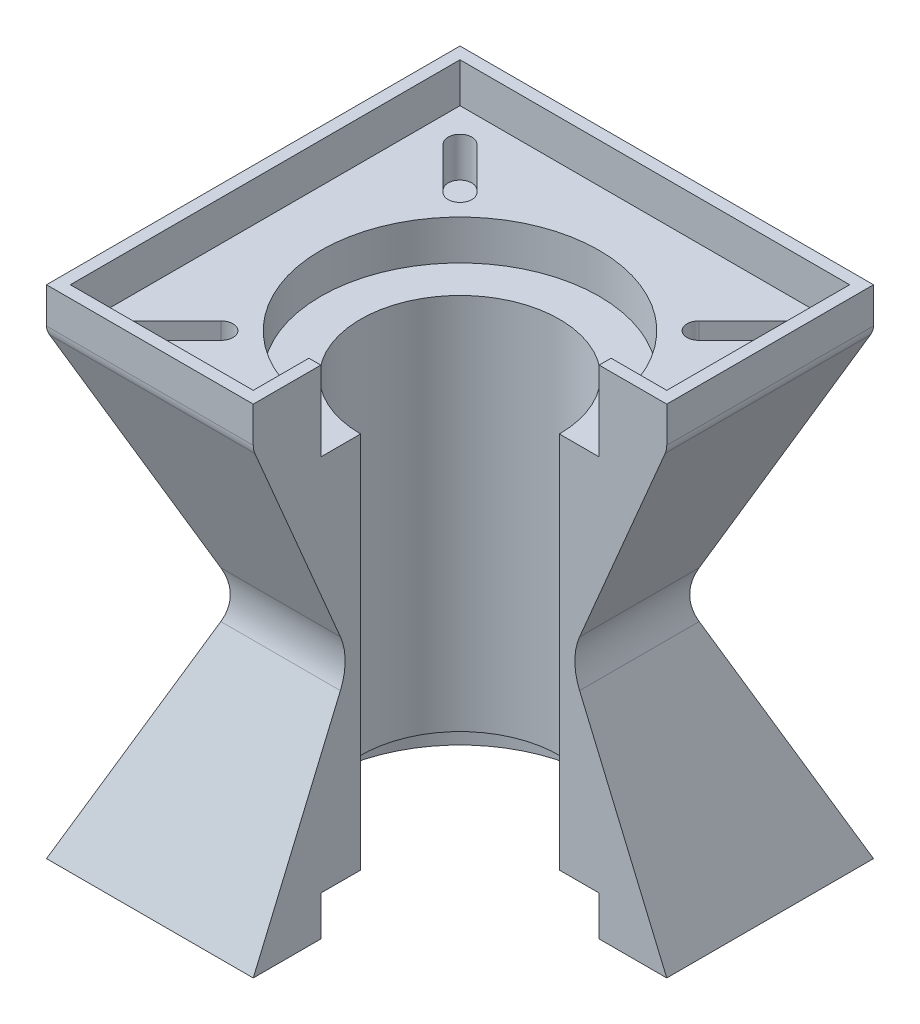
SolidWorks part; units mm, degrees
material "Cast Stainless Steel"
ref_plane "Front Plane" through (0, 0, 0) normal (0, 0, 1) x (1, 0, 0)
ref_plane "Top Plane" through (0, 0, 0) normal (0, 1, 0) x (1, 0, 0)
ref_plane "Right Plane" through (0, 0, 0) normal (1, 0, 0) x (0, 0, -1)
sketch "Sketch1" plane through (0, 0, 0) normal (0, 1, 0) x (1, 0, 0)
  line L1 (-52, 52) -> (52, 52)
  line L2 (-52, 52) -> (-52, -52)
  line L3 (-52, -52) -> (52, -52)
  line L4 (52, 52) -> (52, -52)
  line L5 (-52, 52) -> (52, -52) construction
  line L6 (-52, -52) -> (52, 52) construction
  point P0 (0, 0)
  dimension "D1" = 104
  dimension "D2" = 104
extrude "Boss-Extrude1" add sketch "Sketch1" along normal blind 57.5 draft 23
mirror "Mirror1" about plane through (0, 57.5, 0) normal (0, 1, 0) of bodies 101
sketch "Sketch2" plane through (0, 115, 0) normal (0, 1, 0) x (1, 0, 0)
  circle A0 centre (0, 0) radius 25
  dimension "D1" = 50
extrude "Cut-Extrude1" cut sketch "Sketch2" against normal through all
sketch "Sketch3" plane through (0, 115, 0) normal (0, 1, 0) x (1, 0, 0)
  circle A0 centre (0, 0) radius 35
  point P3 (0, 0)
  dimension "D1" = 70
extrude "Cut-Extrude2" cut sketch "Sketch3" against normal blind 10
sketch "Sketch4" plane through (0, 0, 0) normal (0, -1, 0) x (1, 0, 0)
  circle A0 centre (0, 0) radius 35
  dimension "D1" = 70
extrude "Cut-Extrude3" cut sketch "Sketch4" against normal blind 10
sketch "Sketch5" plane through (0, 115, 0) normal (0, 1, 0) x (1, 0, 0)
  line L1 (0, 0) -> (52, 0)
  line L2 (0, 0) -> (0, -52)
  line L3 (0, -52) -> (52, -52)
  line L4 (52, 0) -> (52, -52)
extrude "Cut-Extrude4" cut sketch "Sketch5" against normal through all
fillet "Fillet1" radius 15 4 edges at (-27.5927, 57.5, 0) (0, 57.5, -27.5927) (27.5927, 57.5, -13.7963) (-13.7963, 57.5, 27.5927)
sketch "Sketch6" plane through (0, 115, 0) normal (0, 1, 0) x (1, 0, 0)
  line L0 (52, 0) -> (52, 52) construction
  line L1 (52, 0) -> (35, 0) construction
  line L2 (0, -35) -> (0, -52) construction
  line L3 (-52, -52) -> (0, -52) construction
  line L4 (-52, 52) -> (-52, -52) construction
  line L5 (52, 52) -> (-52, 52) construction
  line L6 (52, 0) -> (52, 52)
  line L7 (52, 0) -> (35, 0)
  line L8 (0, -35) -> (0, -52)
  line L9 (-52, -52) -> (0, -52)
  line L10 (-52, 52) -> (-52, -52)
  line L11 (52, 52) -> (-52, 52)
  line L12 (49, 3) -> (35, 3)
  line L13 (49, 3) -> (49, 49)
  line L14 (49, 49) -> (-49, 49)
  line L15 (-49, 49) -> (-49, -49)
  line L16 (-49, -49) -> (-3, -49)
  line L17 (-3, -35) -> (-3, -49)
  line L18 (-3, -35) -> (0, -35)
  line L19 (35, 3) -> (35, 0)
  dimension "D1" = 3
extrude "Boss-Extrude2" add sketch "Sketch6" along normal blind 10
sketch "Sketch7" plane through (0, 115, 0) normal (0, 1, 0) x (1, 0, 0)
  line L0 (-49, -49) -> (49, 49) construction
  line L1 (0, 0) -> (-49, 49) construction
  line L2 (0, 0) -> (0, 50) construction
  line L3 (0, 0) -> (-49, 0) construction
  line L4 (-49, -49) -> (-49, 49) construction
  line L5 (-30.052, 30.052) -> (-40.6586, 40.6586) construction
  line L6 (-32.1734, 27.9307) -> (-42.78, 38.5373)
  line L7 (-27.9307, 32.1734) -> (-38.5373, 42.78)
  line L8 (30.052, 30.052) -> (40.6586, 40.6586) construction
  line L9 (32.1734, 27.9307) -> (42.78, 38.5373)
  line L10 (27.9307, 32.1734) -> (38.5373, 42.78)
  line L11 (-30.052, -30.052) -> (-40.6586, -40.6586) construction
  line L12 (-32.1734, -27.9307) -> (-42.78, -38.5373)
  line L13 (-27.9307, -32.1734) -> (-38.5373, -42.78)
  circle A0 centre (0, 0) radius 50 construction
  arc A1 (-32.1734, 27.9307) -> (-27.9307, 32.1734) centre (-30.052, 30.052) ccw
  arc A2 (-38.5373, 42.78) -> (-42.78, 38.5373) centre (-40.6586, 40.6586) ccw
  arc A3 (32.1734, 27.9307) -> (27.9307, 32.1734) centre (30.052, 30.052) cw
  arc A4 (38.5373, 42.78) -> (42.78, 38.5373) centre (40.6586, 40.6586) cw
  arc A5 (-32.1734, -27.9307) -> (-27.9307, -32.1734) centre (-30.052, -30.052) cw
  arc A6 (-38.5373, -42.78) -> (-42.78, -38.5373) centre (-40.6586, -40.6586) cw
  point P5 (0, 0)
  point P16 (-35.3553, 35.3553)
  point P23 (35.3553, 35.3553)
  point P30 (-35.3553, -35.3553)
  dimension "D1" = 100
  dimension "D2" = 3
  dimension "D3" = 15
extrude "Cut-Extrude5" cut sketch "Sketch7" against normal blind 10
fillet "Fillet2" radius 5 4 edges at (-26, 115, 52) (-52, 115, 0) (0, 115, -52) (52, 115, -26)
equation "\"A\"= 115.00mm"
equation "\"B\"= 104.00mm"
equation "\"C\"= 23.00deg"
equation "\"D1@Sketch1\"=\"B\""
equation "\"D2@Sketch1\"=\"B\""
equation "\"D1@Boss-Extrude1\"=\"A\"/2"
equation "\"D3@Boss-Extrude1\"=\"C\""
